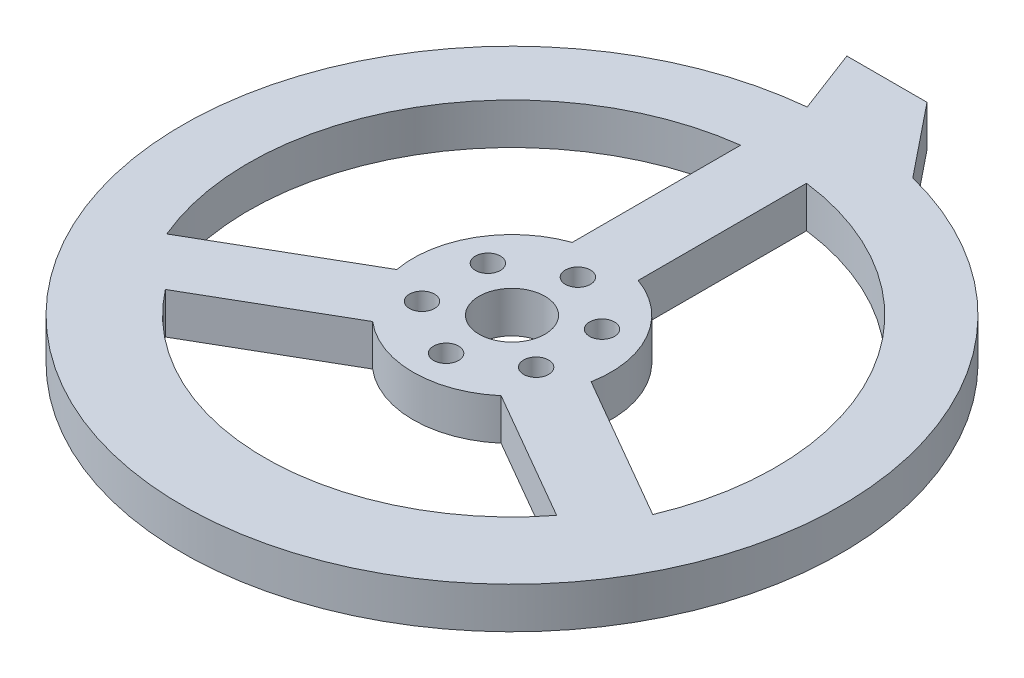
SolidWorks part; units mm, degrees
material "Custom Plastic"
ref_plane "Front Plane" through (0, 0, 0) normal (0, 0, 1) x (1, 0, 0)
ref_plane "Top Plane" through (0, 0, 0) normal (0, 1, 0) x (1, 0, 0)
ref_plane "Right Plane" through (0, 0, 0) normal (1, 0, 0) x (0, 0, -1)
other "Center of Mass"
sketch "Sketch1" plane through (0, 0, 0) normal (0, 1, 0) x (1, 0, 0)
  line L3 (-12.6116, 126.3723) -> (-21.997, 151.0453)
  line L4 (-21.997, 151.0453) -> (8.8989, 151.0453)
  line L5 (8.8989, 151.0453) -> (31.4125, 123.0539)
  line L11 (-37.4585, -6.962) -> (-93.6481, -39.403)
  line L21 (-24.7585, -28.959) -> (-80.9481, -61.4001)
  line L23 (24.7585, -28.959) -> (80.9481, -61.4001)
  line L25 (37.4585, -6.962) -> (93.6481, -39.403)
  line L26 (12.7, 35.921) -> (12.7, 100.8031)
  line L28 (-12.7, 35.921) -> (-12.7, 100.8031)
  arc A0 (-12.6116, 126.3723) -> (31.4125, 123.0539) centre (0, 0) ccw
  circle A1 centre (0, 0) radius 12.7
  circle A2 centre (0, 0) radius 38.1
  arc A3 (80.9481, -61.4001) -> (-80.9481, -61.4001) centre (0, 0) ccw
  circle A5 centre (0, 25.4) radius 4.826
  circle A6 centre (21.997, 12.7) radius 4.826
  circle A7 centre (21.997, -12.7) radius 4.826
  circle A8 centre (0, -25.4) radius 4.826
  circle A9 centre (-21.997, -12.7) radius 4.826
  circle A10 centre (-21.997, 12.7) radius 4.826
  circle A12 centre (0, 0) radius 127 construction
  circle A14 centre (0, 0) radius 101.6 construction
  arc A16 (-75.4024, -58.1983) -> (75.4024, -58.1983) centre (0, 0) ccw
  arc A17 (-71.6945, -62.7093) -> (-69.9322, -55.0401) centre (-66.9787, -59.7559) cw
  point P12 (0, 0)
  point P14 (0, 0)
  point P15 (0, 0)
  point P27 (0, 0)
  dimension "D1" = 254
  dimension "D2" = 25.4
  dimension "D3" = 76.2
  dimension "D5" = 6
  dimension "D6" = 9.652
  dimension "D4" = 25.4
extrude "Boss-Extrude1" add sketch "Sketch1" along normal blind 15.875 contours A2 A1 | L26 A3 L28 A2 | L11 A3 L21 A2 | L23 A3 L25 A2 | A0 A3 region at (-13.7844, 0, -140.0477) region at (-60.0638, 0, 34.6778) region at (-32.0623, 0, -18.5112) region at (0, 0, -69.3557) region at (60.0638, 0, 34.6778)
